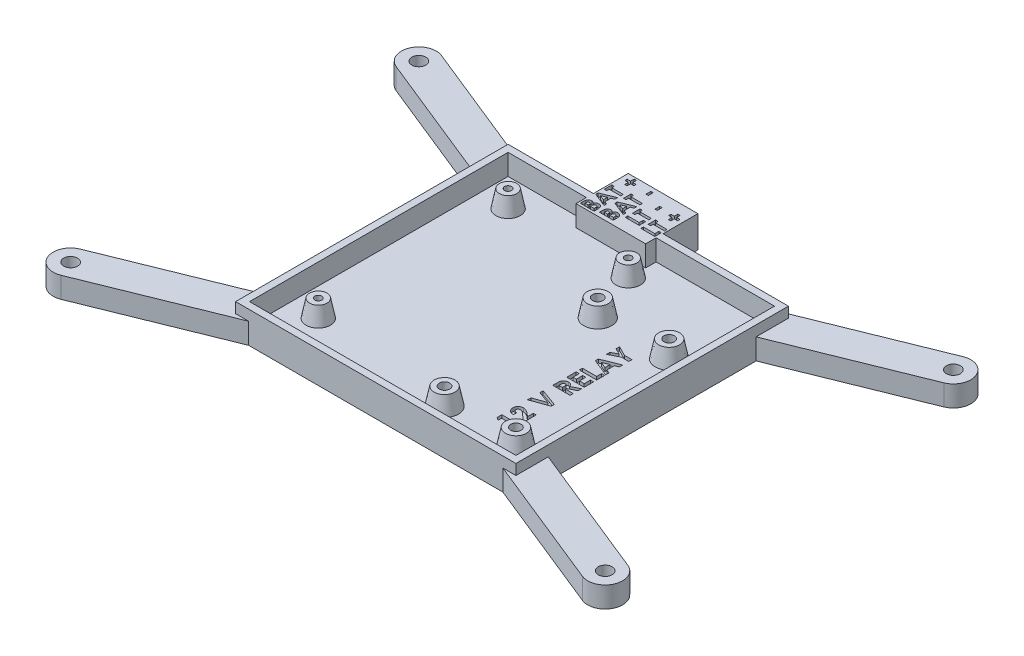
SolidWorks part; units mm, degrees
ref_plane "Front Plane" through (0, 0, 0) normal (0, 0, 1) x (1, 0, 0)
ref_plane "Top Plane" through (0, 0, 0) normal (0, 1, 0) x (1, 0, 0)
ref_plane "Right Plane" through (0, 0, 0) normal (1, 0, 0) x (0, 0, -1)
sketch "Sketch1" plane through (0, 0, 0) normal (0, 1, 0) x (1, 0, 0)
  line L1 (0, 0) -> (34.5, 0) construction
  line L2 (0, 0) -> (0, 54.5) construction
  line L3 (0, 54.5) -> (34.5, 54.5) construction
  line L4 (34.5, 0) -> (34.5, 54.5) construction
  line L5 (17.25, 54.5) -> (17.25, 0) construction
  line L6 (0, 27.25) -> (34.5, 27.25) construction
  line L7 (40, -3.75) -> (60.5, -3.75) construction
  line L8 (40, -3.75) -> (40, 40.25) construction
  line L9 (40, 40.25) -> (60.5, 40.25) construction
  line L10 (60.5, -3.75) -> (60.5, 40.25) construction
  line L11 (50.25, 40.25) -> (50.25, -3.75) construction
  line L12 (40, 18.25) -> (60.5, 18.25) construction
  line L13 (70.5, 64.5) -> (-10, 64.5)
  line L14 (70.5, 64.5) -> (70.5, -13.75)
  line L15 (70.5, -13.75) -> (-10, -13.75)
  line L16 (-10, 64.5) -> (-10, -13.75)
  line L17 (30.25, -13.75) -> (30.25, 64.5) construction
  line L18 (70.5, 25.375) -> (-10, 25.375) construction
  circle A0 centre (0, 54.5) radius 1
  circle A1 centre (34.5, 54.5) radius 1
  circle A2 centre (34.5, 0) radius 1
  circle A3 centre (0, 0) radius 1
  circle A4 centre (0, 54.5) radius 2.5
  circle A5 centre (34.5, 54.5) radius 2.5
  circle A6 centre (34.5, 0) radius 2.5
  circle A7 centre (0, 0) radius 2.5
  circle A8 centre (40, -3.75) radius 1.5
  circle A9 centre (40, -3.75) radius 3
  circle A10 centre (60.5, -3.75) radius 3
  circle A11 centre (60.5, -3.75) radius 1.5
  circle A12 centre (60.5, 40.25) radius 1.5
  circle A13 centre (60.5, 40.25) radius 3
  circle A14 centre (40, 40.25) radius 1.5
  circle A15 centre (40, 40.25) radius 3
  point P228 (17.25, 27.25)
  point P300 (50.25, 18.25)
  point P496 (30.25, 25.375)
  dimension "D3" = 2
  dimension "D6" = 3
  dimension "D11" = 10
  dimension "D1" = 34.5
  dimension "D2" = 54.5
  dimension "D5" = 5.5
  dimension "D7" = 3.75
  dimension "D8" = 20.5
  dimension "D9" = 44
  dimension "D12" = 10
  dimension "D13" = 10
  dimension "D14" = 10
  dimension "D4" = 1.5
  dimension "D10" = 1.5
extrude "Boss-Extrude1" add sketch "Sketch1" against normal blind 3 contours L13 L16 L15 L14 A13 A7 A6 A4 A5 A9 A10 A15 | A4 A0 | A0 | A1 | A5 A1 | A14 | A15 A14 | A13 A12 | A12 | A11 | A10 A11 | A9 A8 | A8 | A2 | A6 A2 | A7 A3 | A3 region at (30.0468, 0, -25.4828) region at (0, 0, -54.5) region at (34.5, 0, -54.5) region at (34.5, 0, 0) region at (0, 0, 0) region at (-2.4293, 0, -54.5) region at (32.0707, 0, -54.5) region at (32.0707, 0, 0) region at (-2.4293, 0, 0) region at (40, 0, 3.75) region at (37.0849, 0, 3.75) region at (57.5849, 0, 3.75) region at (60.5, 0, 3.75) region at (60.5, 0, -40.25) region at (57.5849, 0, -40.25) region at (40, 0, -40.25) region at (37.0849, 0, -40.25)
extrude "Boss-Extrude2" add sketch "Sketch1<3>" along normal blind 5 contours A7 A3 | A4 A0 | A5 A1 | A15 A14 | A9 A8 | A10 A11 | A13 A12 region at (-2.4293, 0, -54.5) region at (32.0707, 0, -54.5) region at (-2.4293, 0, 0) region at (37.0849, 0, 3.75) region at (57.5849, 0, 3.75) region at (57.5849, 0, -40.25) region at (37.0849, 0, -40.25)
sketch "Sketch1<3>" plane through (0, 0, 0) normal (0, 1, 0) x (1, 0, 0) same geometry as "Sketch1"
chamfer "Chamfer1" distance 1 distance2 5 7 edges at (60.5, 0, -37.25) (60.5, 0, 6.75) (40, 0, 6.75) (40, 0, -37.25) (34.5, 0, -52) (0, 0, 2.5) (0, 0, -52) first distance on face at (60.5, 0, -37.25)
sketch "Sketch2" plane through (0, 0, 0) normal (0, 1, 0) x (1, 0, 0)
  line L0 (70.5, 64.5) -> (-10, 64.5) construction
  line L1 (-46.5, -24.625) -> (107, -24.625) construction
  line L2 (-46.5, -24.625) -> (-46.5, 75.375) construction
  line L3 (-46.5, 75.375) -> (107, 75.375) construction
  line L4 (107, -24.625) -> (107, 75.375) construction
  line L5 (30.25, 75.375) -> (30.25, -24.625) construction
  line L6 (-46.5, 25.375) -> (107, 25.375) construction
  line L7 (-10, 64.5) -> (-10, -13.75) construction
  line L8 (-44.6263, 80.0106) -> (-6.2526, 64.5)
  line L9 (-6.2526, 64.5) -> (-10, 55.2287)
  line L10 (-10, 55.2287) -> (-48.3737, 70.7394)
  line L11 (-10, 55.2287) -> (-10, 64.5)
  line L12 (-10, 64.5) -> (-6.2526, 64.5)
  line L13 (70.5, 64.5) -> (66.7526, 64.5)
  line L14 (70.5, 55.2287) -> (70.5, 64.5)
  line L15 (70.5, 55.2287) -> (108.8737, 70.7394)
  line L16 (66.7526, 64.5) -> (70.5, 55.2287)
  line L17 (105.1263, 80.0106) -> (66.7526, 64.5)
  line L18 (105.1263, -29.2606) -> (66.7526, -13.75)
  line L19 (66.7526, -13.75) -> (70.5, -4.4787)
  line L20 (70.5, -4.4787) -> (108.8737, -19.9894)
  line L21 (70.5, -4.4787) -> (70.5, -13.75)
  line L22 (70.5, -13.75) -> (66.7526, -13.75)
  line L23 (-10, -13.75) -> (-6.2526, -13.75)
  line L24 (-10, -4.4787) -> (-10, -13.75)
  line L25 (-10, -4.4787) -> (-48.3737, -19.9894)
  line L26 (-6.2526, -13.75) -> (-10, -4.4787)
  line L27 (-44.6263, -29.2606) -> (-6.2526, -13.75)
  circle A0 centre (-46.5, 75.375) radius 2
  circle A5 centre (-46.5, 75.375) radius 5
  circle A6 centre (107, 75.375) radius 5
  circle A7 centre (107, 75.375) radius 2
  circle A8 centre (107, -24.625) radius 2
  circle A9 centre (107, -24.625) radius 5
  circle A10 centre (-46.5, -24.625) radius 5
  circle A11 centre (-46.5, -24.625) radius 2
  point P6 (30.25, 64.5)
  point P9 (-10, 25.375)
  point P148 (30.25, 25.375)
  line M18 (70.5, 64.5) -> (-10, 64.5)
  line M19 (-10, 64.5) -> (-10, -13.75)
  line M20 (-10, -13.75) -> (70.5, -13.75)
  line M21 (70.5, -13.75) -> (70.5, 64.5)
  dimension "D3" = 4
  dimension "D4" = 10
  dimension "D1" = 153.5
  dimension "D2" = 100
  dimension "D5" = 10
extrude "Boss-Extrude3" add sketch "Sketch2" along normal blind 3 separate body contours A5 A0 | A5 L10 L8 M19 M18 | L15 A6 L17 M18 M21 | A9 L20 L18 M21 M20 | A9 A8 | A6 A7 | A10 A11 | L25 A10 L27 M20 M19 region at (-26.323, 0, -67.1566) region at (-42.4719, 0, -78.0916) region at (86.823, 0, -67.1566) region at (-26.323, 0, 16.4066) region at (109.7166, 0, -79.4031) region at (-43.7834, 0, 20.5969) region at (86.823, 0, 16.4066) region at (111.0281, 0, 21.9084)
sketch "Sketch3" plane through (0, 0, 0) normal (0, 1, 0) x (1, 0, 0)
  line L0 (68.5, 62.5) -> (-8, 62.5)
  line L1 (-8, 62.5) -> (-8, -11.75)
  line L2 (-8, -11.75) -> (68.5, -11.75)
  line L3 (68.5, -11.75) -> (68.5, 62.5)
  line L4 (70.5, 64.5) -> (-10, 64.5)
  line L5 (-10, 64.5) -> (-10, -13.75)
  line L6 (-10, -13.75) -> (70.5, -13.75)
  line L7 (70.5, -13.75) -> (70.5, 64.5)
  line L8 (70.5, 64.5) -> (-10, 64.5)
  line L9 (-10, 64.5) -> (-10, -13.75)
  line L10 (-10, -13.75) -> (70.5, -13.75)
  line L11 (70.5, -13.75) -> (70.5, 64.5)
  dimension "D1" = 0
  dimension "D2" = 2
extrude "Boss-Extrude4" add sketch "Sketch3" along normal blind 6
sketch "Sketch4" plane through (0, 0, 0) normal (0, -1, 0) x (1, 0, 0)
  line L0 (66.7526, 13.75) -> (105.1263, 29.2606)
  line L1 (-10, -64.5) -> (70.5, -64.5)
  line L2 (-10, -64.5) -> (-10, 13.75)
  line L3 (-10, 13.75) -> (70.5, 13.75)
  line L4 (70.5, -64.5) -> (70.5, 13.75)
  line L5 (30.25, 13.75) -> (30.25, -64.5) construction
  line L6 (-10, -25.375) -> (70.5, -25.375) construction
  line L7 (70.5, 13.75) -> (66.7526, 13.75)
  line L8 (70.5, 4.4787) -> (70.5, 13.75)
  line L9 (108.8737, 19.9894) -> (70.5, 4.4787)
  line L10 (-48.3737, 19.9894) -> (-10, 4.4787)
  line L11 (-10, 4.4787) -> (-10, 13.75)
  line L12 (-10, 13.75) -> (-6.2526, 13.75)
  line L13 (-6.2526, 13.75) -> (-44.6263, 29.2606)
  line L14 (-48.3737, 19.9894) -> (-10, 4.4787)
  line L15 (-10, 4.4787) -> (-10, 13.75)
  line L16 (-10, 13.75) -> (-6.2526, 13.75)
  line L17 (-6.2526, 13.75) -> (-44.6263, 29.2606)
  line L18 (108.8737, -70.7394) -> (70.5, -55.2287)
  line L19 (70.5, -55.2287) -> (70.5, -64.5)
  line L20 (70.5, -64.5) -> (66.7526, -64.5)
  line L21 (66.7526, -64.5) -> (105.1263, -80.0106)
  line L22 (-6.2526, -64.5) -> (-44.6263, -80.0106)
  line L23 (-10, -64.5) -> (-6.2526, -64.5)
  line L24 (-10, -55.2287) -> (-10, -64.5)
  line L25 (-48.3737, -70.7394) -> (-10, -55.2287)
  circle A0 centre (-46.5, 24.625) radius 2.5
  arc A1 (-44.6263, 29.2606) -> (-48.3737, 19.9894) centre (-46.5, 24.625) ccw
  arc A2 (-44.6263, 29.2606) -> (-48.3737, 19.9894) centre (-46.5, 24.625) ccw
  arc A3 (105.1263, 29.2606) -> (108.8737, 19.9894) centre (107, 24.625) cw
  circle A4 centre (107, 24.625) radius 2.5
  circle A5 centre (107, -75.375) radius 2.5
  arc A6 (105.1263, -80.0106) -> (108.8737, -70.7394) centre (107, -75.375) ccw
  arc A7 (-44.6263, -80.0106) -> (-48.3737, -70.7394) centre (-46.5, -75.375) cw
  circle A8 centre (-46.5, -75.375) radius 2.5
  point P244 (30.25, -25.375)
  arc M8 (-44.6263, 29.2606) -> (-48.3737, 19.9894) centre (-46.5, 24.625) ccw
  line M9 (-48.3737, 19.9894) -> (-10, 4.4787)
  line M10 (-10, 4.4787) -> (-10, 13.75)
  line M11 (-10, 13.75) -> (-6.2526, 13.75)
  line M12 (-6.2526, 13.75) -> (-44.6263, 29.2606)
  dimension "D2" = 5
  dimension "D1" = 0
extrude "Boss-Extrude5" add sketch "Sketch4" along normal up to surface (3 mm away) contours A0 M12 M8 M9 M10 M11 | A7 L22 L1 L2 L25 A8 | L21 A6 L18 L4 L1 A5 | A3 L0 L3 L4 L9 A4 region at (89.6789, 0, 17.5699) region at (-29.1789, 0, 17.5699) region at (89.6789, 0, -68.3199) region at (-29.1789, 0, -68.3199) up to face at (30.25, -3, -25.375)
sketch "Sketch5" plane through (0, 6, 0) normal (0, 1, 0) x (1, 0, 0)
  line L1 (34.5, 59.5) -> (14.5, 59.5)
  line L2 (34.5, 59.5) -> (34.5, 74.5)
  line L3 (34.5, 74.5) -> (14.5, 74.5)
  line L4 (14.5, 59.5) -> (14.5, 74.5)
  line L5 (24.5, 74.5) -> (24.5, 59.5) construction
  line L6 (34.5, 67) -> (14.5, 67) construction
  line L7 (34.5, 54.5) -> (34.5, 59.5) construction
  point P4 (24.5, 59.5)
  point P240 (24.5, 67)
  dimension "D1" = 20
  dimension "D2" = 15
  dimension "D3" = 5
extrude "Boss-Extrude6" add sketch "Sketch5" against normal up to surface (9 mm away) up to face at (30.25, -3, -25.375)
sketch "Sketch6" plane through (0, 6, 0) normal (0, 1, 0) x (1, 0, 0)
  line L0 (34, 74.5) -> (34, 59.5) construction
  line L1 (29, 74.5) -> (29, 59.5) construction
  line L2 (24, 74.5) -> (24, 59.5) construction
  line L3 (19, 74.5) -> (19, 59.5) construction
  line L4 (34.5, 64.5) -> (34.5, 74.5) construction
  text T0 "LT +" font "Century Gothic" height 4
  text T1 "LT -" font "Century Gothic" height 4
  text T2 "BAT -" font "Century Gothic" height 4
  text T3 "BAT +" font "Century Gothic" height 4
  point P11 (0, 0)
  dimension "D2" = 0.5
  dimension "D1" = 4
extrude "Cut-Extrude1" cut sketch "Sketch6" against normal blind 1
sketch "Sketch7" plane through (0, 0, 0) normal (0, 1, 0) x (1, 0, 0)
  line L0 (55.352, 40.25) -> (55.352, -3.75) construction
  text T0 "12 V RELAY" font "Century Gothic" height 5
extrude "Cut-Extrude2" cut sketch "Sketch7" against normal blind 1
